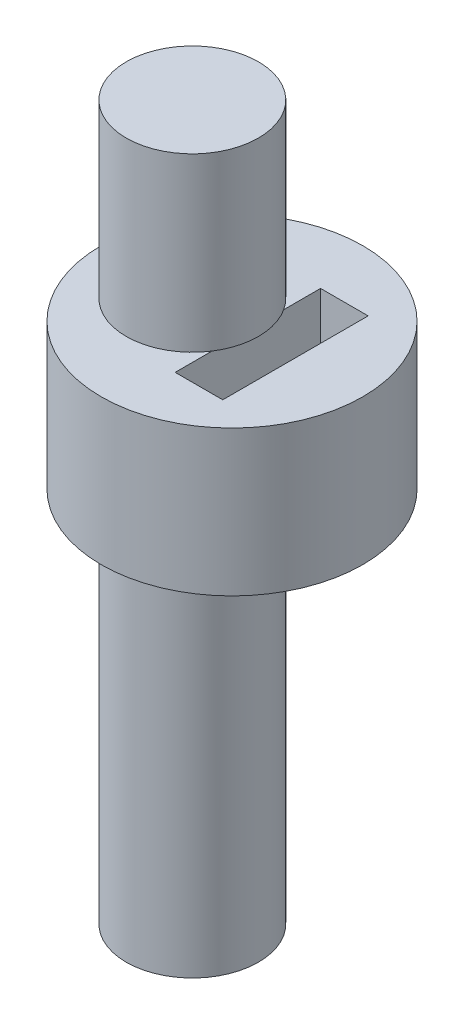
SolidWorks part; units mm, degrees
ref_plane "Front Plane" through (0, 0, 0) normal (0, 0, 1) x (1, 0, 0)
ref_plane "Top Plane" through (0, 0, 0) normal (0, 1, 0) x (1, 0, 0)
ref_plane "Right Plane" through (0, 0, 0) normal (1, 0, 0) x (0, 0, -1)
sketch "Sketch1" plane through (0, 0, 0) normal (0, 1, 0) x (1, 0, 0)
  circle A0 centre (0, 0) radius 2.5
  circle A1 centre (0, 0) radius 2.55 construction
  dimension "D1" = 5
  dimension "D2" = 5.1
extrude "Boss-Extrude1" add sketch "Sketch1" along normal blind 15
sketch "Sketch2" plane through (0, 15, 0) normal (0, 1, 0) x (1, 0, 0)
  circle A0 centre (1.5, 0) radius 4.95
  dimension "D1" = 9.9
  dimension "D2" = 1.5
extrude "Boss-Extrude2" add sketch "Sketch2" along normal blind 5.5
sketch "Sketch3" plane through (0, 20.5, 0) normal (0, 1, 0) x (1, 0, 0)
  circle A2 centre (0, 0) radius 2.5 construction
  circle A3 centre (0, 0) radius 2.5
extrude "Boss-Extrude3" add sketch "Sketch3" along normal blind 6.5
sketch "Sketch4" [suppressed] plane through (0, 27, 0) normal (0, 1, 0) x (1, 0, 0)
  line L0 (-2.0842, 3.4141) -> (-1.5, 0)
  line L1 (-1.5, 0) -> (-2.0842, -3.4141)
  circle A0 centre (0, 0) radius 2.5 construction
  circle A1 centre (0, 0) radius 2.5 construction
  arc A2 (-2.0842, 3.4141) -> (-2.0842, -3.4141) centre (0, 0) ccw
  circle A3 centre (1.5, 0) radius 4.95 construction
  dimension "D1" = 1.5
extrude "Cut-Extrude1" [suppressed] cut sketch "Sketch4" against normal up to surface (6.5 mm away) up to face at (0, 20.5, 2.5)
fillet "Fillet1" [suppressed] radius 1
sketch "Sketch6" plane through (0, 0, 0) normal (0, -1, 0) x (1, 0, 0)
  line L1 (-3.6662, 0) -> (-1.8331, -3.175)
  line L2 (-1.8331, -3.175) -> (1.8331, -3.175)
  line L3 (1.8331, -3.175) -> (3.6662, 0)
  line L4 (3.6662, 0) -> (1.8331, 3.175)
  line L5 (1.8331, 3.175) -> (-1.8331, 3.175)
  line L6 (-1.8331, 3.175) -> (-3.6662, 0)
  circle A0 centre (0, 0) radius 3.175 construction
  dimension "D1" = 6.35
extrude "Cut-Extrude2" [suppressed] cut sketch "Sketch6" against normal blind 6 flip side to cut
fillet "Fillet2" [suppressed] radius 0.5
sketch "Sketch7" plane through (0, 15, 0) normal (0, -1, 0) x (1, 0, 0)
  line L0 (2, 1.5) -> (2, -1.5) construction
  line L1 (2.1, 2.75) -> (3.9, 2.75)
  line L2 (2.1, 2.75) -> (2.1, -2.75)
  line L3 (2.1, -2.75) -> (3.9, -2.75)
  line L4 (3.9, 2.75) -> (3.9, -2.75)
  line L5 (2.1, 2.75) -> (3.9, -2.75) construction
  line L6 (2.1, -2.75) -> (3.9, 2.75) construction
  circle A0 centre (1.5, 0) radius 4.95 construction
  circle A1 centre (0, 0) radius 2.5 construction
  circle A2 centre (1.5, 0) radius 4.95 construction
  circle A3 centre (0, 0) radius 2.5 construction
  point P6 (3, 0)
  dimension "D1" = 3.95
  dimension "D2" = 1.8
  dimension "D3" = 5.5
  dimension "D4" = 4.5
  dimension "D5" = 0.2
extrude "Cut-Extrude3" cut sketch "Sketch7" against normal up to surface (5.5 mm away) up to face at (0, 20.5, 2.5)
